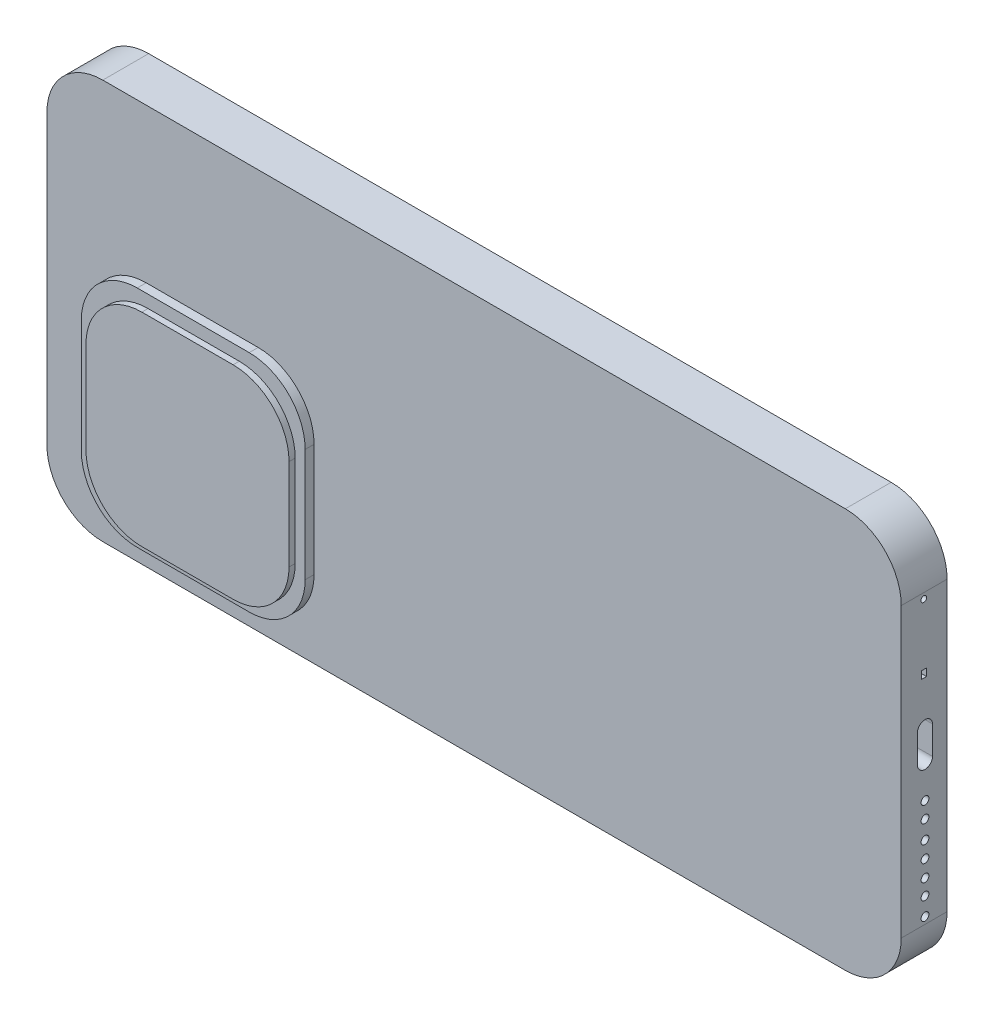
SolidWorks part; units mm, degrees
ref_plane "前视基准面" through (0, 0, 0) normal (0, 0, 1) x (1, 0, 0)
ref_plane "上视基准面" through (0, 0, 0) normal (0, 1, 0) x (1, 0, 0)
ref_plane "右视基准面" through (0, 0, 0) normal (1, 0, 0) x (0, 0, -1)
sketch "草图1" plane through (0, 0, 0) normal (0, 0, 1) x (1, 0, 0)
  line L1 (-10, 0) -> (-142.8, 0)
  line L2 (0, 10) -> (0, 61.5)
  line L3 (-10, 71.5) -> (-142.8, 71.5)
  line L4 (-152.8, 10) -> (-152.8, 61.5)
  arc A0 (-10, 0) -> (0, 10) centre (-10, 10) ccw
  arc A1 (-10, 71.5) -> (0, 61.5) centre (-10, 61.5) cw
  arc A2 (-142.8, 71.5) -> (-152.8, 61.5) centre (-142.8, 61.5) ccw
  arc A3 (-142.8, 0) -> (-152.8, 10) centre (-142.8, 10) cw
  point P7 (0, 0)
  dimension "D1" = 10
  dimension "D2" = 10
  dimension "D3" = 10
  dimension "D4" = 10
extrude "凸台-拉伸1" add sketch "草图1" along normal blind 8.2 contours L3 A2 L4 A3 L1 A0 L2 A1
sketch "草图3" plane through (0, 0, 0) normal (0, 0, 1) x (1, 0, 0)
  line L1 (-135.046, 43.9786) -> (-115.0149, 43.9786)
  line L2 (-145.046, 33.9786) -> (-145.046, 13.7992)
  line L3 (-135.046, 3.7992) -> (-115.0149, 3.7992)
  line L4 (-105.0149, 33.9786) -> (-105.0149, 13.7992)
  arc A0 (-145.046, 13.7992) -> (-135.046, 3.7992) centre (-135.046, 13.7992) ccw
  arc A1 (-115.0149, 3.7992) -> (-105.0149, 13.7992) centre (-115.0149, 13.7992) ccw
  arc A2 (-115.0149, 43.9786) -> (-105.0149, 33.9786) centre (-115.0149, 33.9786) cw
  arc A3 (-135.046, 43.9786) -> (-145.046, 33.9786) centre (-135.046, 33.9786) ccw
  dimension "D1" = 10
extrude "凸台-拉伸2" add sketch "草图3" along normal blind 9.8 contours A3 L2 A0 L3 A1 L4 A2 L1
sketch "草图4" plane through (0, 0, 0) normal (0, 0, 1) x (1, 0, 0)
  line L1 (-133.1186, 41.7547) -> (-116.794, 41.7547)
  line L2 (-143.1186, 31.7547) -> (-143.1186, 15.4301)
  line L3 (-133.1186, 5.4301) -> (-116.794, 5.4301)
  line L4 (-106.794, 31.7547) -> (-106.794, 15.4301)
  arc A0 (-116.794, 5.4301) -> (-106.794, 15.4301) centre (-116.794, 15.4301) ccw
  arc A1 (-143.1186, 15.4301) -> (-133.1186, 5.4301) centre (-133.1186, 15.4301) ccw
  arc A2 (-116.794, 41.7547) -> (-106.794, 31.7547) centre (-116.794, 31.7547) cw
  arc A3 (-133.1186, 41.7547) -> (-143.1186, 31.7547) centre (-133.1186, 31.7547) ccw
  dimension "D1" = 10
extrude "凸台-拉伸4" add sketch "草图4" along normal blind 10.9 contours A3 L2 A1 L3 A0 L4 A2 L1
sketch "草图7" plane through (0, 0, 0) normal (1, 0, 0) x (0, 0, -1)
  line L0 (-3.953, 40.3738) -> (-3.953, 35.346) construction
  line L1 (-2.6063, 40.3738) -> (-2.6063, 35.346)
  line L2 (-5.2998, 40.3738) -> (-5.2998, 35.346)
  arc A0 (-2.6063, 40.3738) -> (-5.2998, 40.3738) centre (-3.953, 40.3738) ccw
  arc A1 (-5.2998, 35.346) -> (-2.6063, 35.346) centre (-3.953, 35.346) ccw
  circle A2 centre (-4.1, 8.3406) radius 0.84
  circle A3 centre (-4.1, 11.2438) radius 0.84
  circle A4 centre (-4.1, 14.3784) radius 0.84
  circle A5 centre (-4.1, 17.1864) radius 0.84
  circle A6 centre (-4.1, 20.0713) radius 0.84
  circle A7 centre (-4.1, 22.8666) radius 0.84
  circle A8 centre (-4.1, 25.4828) radius 0.9258
  point P2 (-3.953, 37.8599)
sketch "草图8" plane through (0, 0, 0) normal (0, 0, -1) x (-1, 0, 0)
  line L1 (141.9492, 69.3122) -> (11.754, 69.3122)
  line L2 (151.9492, 59.3122) -> (151.9492, 11.5201)
  line L3 (141.9492, 1.5201) -> (11.754, 1.5201)
  line L4 (1.754, 59.3122) -> (1.754, 11.5201)
  circle A0 centre (145.7428, 36.8688) radius 1.2769
  arc A1 (141.9492, 69.3122) -> (151.9492, 59.3122) centre (141.9492, 59.3122) cw
  arc A2 (151.9492, 11.5201) -> (141.9492, 1.5201) centre (141.9492, 11.5201) cw
  arc A3 (11.754, 69.3122) -> (1.754, 59.3122) centre (11.754, 59.3122) ccw
  arc A4 (11.754, 1.5201) -> (1.754, 11.5201) centre (11.754, 11.5201) cw
  dimension "D1" = 10
  dimension "D2" = 10
  dimension "D3" = 10
  dimension "D4" = 10
extrude "切除-拉伸2" cut sketch "草图7" against normal blind 5 contours L1 A1 L2 A0
sketch "草图10" plane through (-5, 0, 0) normal (1, 0, 0) x (0, 0, -1)
  line L1 (-4.1011, 40.3757) -> (-3.731, 40.3757)
  line L2 (-4.1011, 40.3757) -> (-4.1011, 35.1209)
  line L3 (-4.1011, 35.1209) -> (-3.731, 35.1209)
  line L4 (-3.731, 40.3757) -> (-3.731, 35.1209)
extrude "凸台-拉伸7" add sketch "草图10" along normal blind 3
sketch "草图11" plane through (0, 0, 0) normal (1, 0, 0) x (0, 0, -1)
  circle A0 centre (-3.952, 29.2) radius 0.7021
  circle A1 centre (-3.952, 26.3135) radius 0.7
  circle A2 centre (-3.952, 23.057) radius 0.7
  circle A3 centre (-3.952, 20.1623) radius 0.7
  circle A5 centre (-3.952, 17.2005) radius 0.7
  circle A7 centre (-3.952, 14.3888) radius 0.7
  circle A9 centre (-3.952, 11.2077) radius 0.7
  point P14 (0, 0)
  point P15 (0, 0)
  point P16 (0, 0)
  point P17 (0, 0)
  point P18 (0, 0)
  point P19 (0, 0)
  point P20 (0, 0)
  point P21 (0, 0)
  point P22 (0, 0)
sketch "草图14" plane through (0, 0, 8.2) normal (0, 0, 1) x (1, 0, 0)
  text T0 "xiaomi"
extrude "切除-拉伸7" cut sketch "草图11" against normal blind 3 contours A7 | A9 | A5 | A3 | A2 | A1 | A0
sketch "草图15" plane through (0, 0, 10.9) normal (0, 0, 1) x (1, 0, 0)
  circle A0 centre (-134.4018, 15.4301) radius 5.9927
  circle A1 centre (-134.4018, 31.7547) radius 5.9743
  circle A2 centre (-115.8766, 15.4301) radius 5.9346
  circle A3 centre (-115.8766, 31.7547) radius 5.913
  point P8 (0, 0)
sketch "草图16" plane through (0, 0, 0) normal (0, -1, 0) x (-1, 0, 0)
  line L0 (122.9031, -3.8548) -> (108.1674, -3.8548) construction
  line L1 (122.9031, -4.4994) -> (108.1674, -4.4994)
  line L2 (122.9031, -3.2101) -> (108.1674, -3.2101)
  line L3 (94.7672, -3.8548) -> (90.5307, -3.8548) construction
  line L4 (94.7672, -4.4534) -> (90.5307, -4.4534)
  line L5 (94.7672, -3.2561) -> (90.5307, -3.2561)
  arc A0 (122.9031, -4.4994) -> (122.9031, -3.2101) centre (122.9031, -3.8548) ccw
  arc A1 (108.1674, -3.2101) -> (108.1674, -4.4994) centre (108.1674, -3.8548) ccw
  arc A2 (94.7672, -4.4534) -> (94.7672, -3.2561) centre (94.7672, -3.8548) ccw
  arc A3 (90.5307, -3.2561) -> (90.5307, -4.4534) centre (90.5307, -3.8548) ccw
  point P2 (115.5352, -3.8548)
  point P7 (92.649, -3.8548)
  point P14 (0, 0)
  point P15 (0, 0)
  point P16 (0, 0)
  point P17 (0, 0)
  point P18 (0, 0)
  point P19 (0, 0)
  point P20 (0, 0)
  point P21 (0, 0)
  point P22 (0, 0)
  point P23 (0, 0)
  point P24 (0, 0)
extrude "凸台-拉伸9" add sketch "草图16" along normal blind 1 contours L2 A1 L1 A0
sketch "草图17" plane through (0, 0, 0) normal (0, -1, 0) x (-1, 0, 0)
  line L0 (98.4261, -4.0321) -> (93.5186, -4.0321) construction
  line L1 (98.4261, -4.6742) -> (93.5186, -4.6742)
  line L2 (98.4261, -3.39) -> (93.5186, -3.39)
  arc A0 (98.4261, -4.6742) -> (98.4261, -3.39) centre (98.4261, -4.0321) ccw
  arc A1 (93.5186, -3.39) -> (93.5186, -4.6742) centre (93.5186, -4.0321) ccw
  point P2 (95.9723, -4.0321)
extrude "凸台-拉伸10" add sketch "草图17" along normal blind 1
sketch "草图18" plane through (0, 0, 0) normal (1, 0, 0) x (0, 0, -1)
  line L0 (-4.1722, 60.5032) -> (-4.1722, 50.4469) construction
  line L1 (-3.3467, 60.5032) -> (-3.3467, 50.4469)
  line L2 (-4.9977, 60.5032) -> (-4.9977, 50.4469)
  arc A0 (-3.3467, 60.5032) -> (-4.9977, 60.5032) centre (-4.1722, 60.5032) ccw
  arc A1 (-4.9977, 50.4469) -> (-3.3467, 50.4469) centre (-4.1722, 50.4469) ccw
  circle A2 centre (-4.1722, 60.5032) radius 0.5253
  point P2 (-4.1722, 55.475)
  point P9 (0, 0)
  point P10 (0, 0)
  point P11 (0, 0)
  point P12 (0, 0)
  point P13 (0, 0)
  point P14 (0, 0)
extrude "切除-拉伸8" cut sketch "草图18" against normal blind 2 contours A2
sketch "草图19" plane through (0, 0, 0) normal (1, 0, 0) x (0, 0, -1)
  line L0 (-4.1, 61.5) -> (-4.1, 54.8975) construction
  line L1 (-8.2, 61.5) -> (0, 61.5) construction
  line L2 (-3.2029, 61.5) -> (-3.2029, 54.8975)
  line L3 (-4.9971, 61.5) -> (-4.9971, 54.8975)
  line L5 (-4.5733, 49.5942) -> (-3.6856, 49.5942)
  line L6 (-4.5733, 49.5942) -> (-4.5733, 48.257)
  line L7 (-4.5733, 48.257) -> (-3.6856, 48.257)
  line L8 (-3.6856, 49.5942) -> (-3.6856, 48.257)
  arc A0 (-3.2029, 61.5) -> (-4.9971, 61.5) centre (-4.1, 61.5) ccw
  arc A1 (-4.9971, 54.8975) -> (-3.2029, 54.8975) centre (-4.1, 54.8975) ccw
  point P4 (-4.1, 58.1988)
extrude "切除-拉伸9" cut sketch "草图19" against normal blind 2 contours L6 L7 L8 L5
sketch "草图20" plane through (0, 0, 0) normal (1, 0, 0) x (0, 0, -1)
  line L0 (-4.1957, 62.0791) -> (-4.1957, 53.5238) construction
  line L1 (-3.2201, 62.0791) -> (-3.2201, 53.5238)
  line L2 (-5.1714, 62.0791) -> (-5.1714, 53.5238)
  arc A0 (-3.2201, 62.0791) -> (-5.1714, 62.0791) centre (-4.1957, 62.0791) ccw
  arc A1 (-5.1714, 53.5238) -> (-3.2201, 53.5238) centre (-4.1957, 53.5238) ccw
  point P2 (-4.1957, 57.8015)
